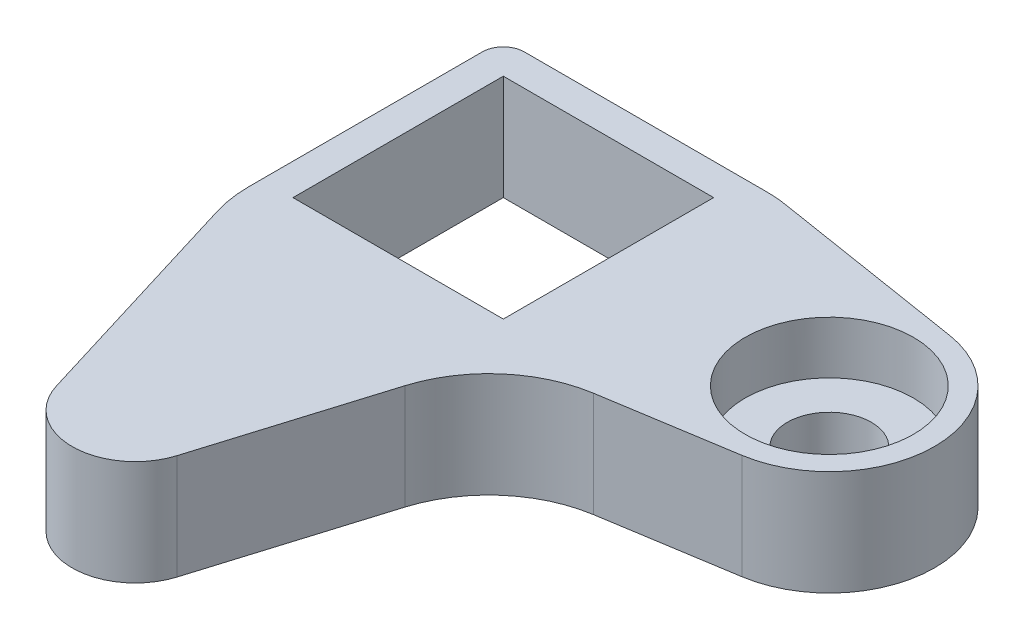
SolidWorks part; units mm, degrees
ref_plane "Front Plane" through (0, 0, 0) normal (0, 0, 1) x (1, 0, 0)
ref_plane "Top Plane" through (0, 0, 0) normal (0, 1, 0) x (1, 0, 0)
ref_plane "Right Plane" through (0, 0, 0) normal (1, 0, 0) x (0, 0, -1)
sketch "Sketch1" plane through (0, 0, 0) normal (0, 1, 0) x (1, 0, 0)
  line L0 (20, 0) -> (41, -10) construction
  line L1 (10, -45) -> (0, -20) construction
  line L2 (41, -10) -> (20, -20) construction
  line L3 (0, 0) -> (0, -20) construction
  line L4 (0, 0) -> (20, -20) construction
  line L5 (23.9399, 2.85) -> (42.5764, -0.125)
  line L12 (-3, -23) -> (23, -23) construction
  line L13 (0, 0) -> (20, 0) construction
  line L14 (0, 0) -> (0, -20) construction
  line L15 (0, -20) -> (20, -20) construction
  line L16 (20, 0) -> (20, -20) construction
  line L17 (10, -45) -> (20, -20) construction
  line L18 (-3, -21.2066) -> (-3, 1)
  line L19 (-1, 3) -> (22.0482, 3)
  line L20 (23, -23) -> (23, 3) construction
  line L21 (-3, -23) -> (23, 3) construction
  line L22 (-3, 3) -> (23, -23) construction
  line L23 (0, -20) -> (20, -20)
  line L24 (0, -20) -> (0, 0)
  line L25 (0, 0) -> (20, 0)
  line L26 (20, -20) -> (20, 0)
  line L27 (0, -20) -> (20, 0) construction
  line L28 (0, 0) -> (20, -20) construction
  line L29 (30.3947, -21.8196) -> (42.5764, -19.875)
  line L30 (20.8107, -30.1612) -> (15.7378, -46.7542)
  line L31 (-2.4757, -24.715) -> (4.2622, -46.7542)
  circle A4 centre (10, -45) radius 4 construction
  circle A5 centre (41, -10) radius 4 construction
  arc A6 (-3, 1) -> (-1, 3) centre (-1, 1) cw
  circle A7 centre (41, -10) radius 8 construction
  arc A8 (42.5764, -19.875) -> (42.5764, -0.125) centre (41, -10) ccw
  arc A9 (4.2622, -46.7542) -> (15.7378, -46.7542) centre (10, -45) ccw
  arc A10 (30.3947, -21.8196) -> (20.8107, -30.1612) centre (32.2864, -33.6695) ccw
  arc A11 (23.9399, 2.85) -> (22.0482, 3) centre (22.0482, -9) ccw
  arc A12 (-3, -21.2066) -> (-2.4757, -24.715) centre (9, -21.2066) ccw
  point P0 (10, -10)
  point P10 (10, -10)
  dimension "D6" = 8
  dimension "D7" = 16
  dimension "D8" = 20
  dimension "D9" = 12
  dimension "D10" = 12
  dimension "D11" = 12
  dimension "D5" = 2
  dimension "D2" = 20
  dimension "D3" = 3
  dimension "D4" = 45
  dimension "D12" = 20
  dimension "D13" = 41
extrude "Boss-Extrude1" add sketch "Sketch1" along normal blind 10
ref_plane "Plane1" through (0, 5, 0) normal (0, 1, 0) x (1, 0, 0)
sketch "Sketch2" plane through (0, 5, 0) normal (0, 1, 0) x (1, 0, 0)
  line L0 (20, 0) -> (41, -10) construction
  line L1 (10, -45) -> (0, -20) construction
  line L2 (41, -10) -> (20, -20) construction
  line L3 (0, 0) -> (0, -20) construction
  line L4 (0, 0) -> (20, -20) construction
  line L5 (23.9399, 2.85) -> (42.5764, -0.125) construction
  line L6 (-3, -23) -> (23, -23) construction
  line L7 (0, 0) -> (20, 0) construction
  line L8 (0, 0) -> (0, -20) construction
  line L9 (0, -20) -> (20, -20) construction
  line L10 (20, 0) -> (20, -20) construction
  line L11 (10, -45) -> (20, -20) construction
  line L12 (-3, -21.2066) -> (-3, 1) construction
  line L13 (-1, 3) -> (22.0482, 3) construction
  line L14 (23, -23) -> (23, 3) construction
  line L15 (-3, -23) -> (23, 3) construction
  line L16 (-3, 3) -> (23, -23) construction
  line L17 (0, -20) -> (20, -20) construction
  line L18 (0, -20) -> (0, 0) construction
  line L19 (0, 0) -> (20, 0) construction
  line L20 (20, -20) -> (20, 0) construction
  line L21 (0, -20) -> (20, 0) construction
  line L22 (0, 0) -> (20, -20) construction
  line L23 (30.3947, -21.8196) -> (42.5764, -19.875) construction
  line L24 (20.8107, -30.1612) -> (15.7378, -46.7542) construction
  line L25 (-2.4757, -24.715) -> (4.2622, -46.7542) construction
  circle A0 centre (10, -45) radius 4 construction
  circle A1 centre (41, -10) radius 4 construction
  arc A2 (-3, 1) -> (-1, 3) centre (-1, 1) cw construction
  circle A3 centre (41, -10) radius 8
  arc A4 (42.5764, -19.875) -> (42.5764, -0.125) centre (41, -10) ccw construction
  arc A5 (4.2622, -46.7542) -> (15.7378, -46.7542) centre (10, -45) ccw construction
  arc A6 (30.3947, -21.8196) -> (20.8107, -30.1612) centre (32.2864, -33.6695) ccw construction
  arc A7 (23.9399, 2.85) -> (22.0482, 3) centre (22.0482, -9) ccw construction
  arc A8 (-3, -21.2066) -> (-2.4757, -24.715) centre (9, -21.2066) ccw construction
  point P0 (10, -10)
  point P10 (10, -10)
  dimension "D2" = 8
  dimension "D7" = 2
  dimension "D8" = 16
  dimension "D9" = 20
  dimension "D10" = 12
  dimension "D11" = 12
  dimension "D12" = 12
  dimension "D1" = 20
  dimension "D3" = 20
  dimension "D4" = 41
  dimension "D5" = 45
  dimension "D6" = 3
sketch "Sketch3" plane through (0, 5, -5) normal (0, -1, 0) x (1, 0, 0)
  line L13 (-1, 2) -> (22.0482, 2) construction
  line L27 (-1, 2) -> (22.0482, 2) construction
  line L28 (-2.4757, 29.715) -> (4.2622, 51.7542) construction
  line L29 (20.8107, 35.1612) -> (15.7378, 51.7542) construction
  line L30 (30.3947, 26.8196) -> (42.5764, 24.875) construction
  line L31 (0, 5) -> (20, 25) construction
  line L32 (0, 25) -> (20, 5) construction
  line L33 (20, 25) -> (20, 5) construction
  line L34 (0, 5) -> (20, 5) construction
  line L35 (0, 25) -> (0, 5) construction
  line L36 (0, 25) -> (20, 25) construction
  line L37 (-3, 2) -> (23, 28) construction
  line L38 (-3, 28) -> (23, 2) construction
  line L39 (23, 28) -> (23, 2) construction
  line L40 (-3, 26.2066) -> (-3, 4) construction
  line L41 (10, 50) -> (20, 25) construction
  line L42 (20, 5) -> (20, 25) construction
  line L43 (0, 25) -> (20, 25) construction
  line L44 (0, 5) -> (0, 25) construction
  line L45 (0, 5) -> (20, 5) construction
  line L46 (-3, 28) -> (23, 28) construction
  line L47 (23.9399, 2.15) -> (42.5764, 5.125) construction
  line L48 (0, 5) -> (20, 25) construction
  line L49 (0, 5) -> (0, 25) construction
  line L50 (41, 15) -> (20, 25) construction
  line L51 (10, 50) -> (0, 25) construction
  line L52 (20, 5) -> (41, 15) construction
  arc A9 (-3, 26.2066) -> (-2.4757, 29.715) centre (9, 26.2066) cw construction
  arc A10 (23.9399, 2.15) -> (22.0482, 2) centre (22.0482, 14) cw construction
  arc A11 (30.3947, 26.8196) -> (20.8107, 35.1612) centre (32.2864, 38.6695) cw construction
  arc A12 (4.2622, 51.7542) -> (15.7378, 51.7542) centre (10, 50) cw construction
  arc A13 (42.5764, 24.875) -> (42.5764, 5.125) centre (41, 15) cw construction
  arc A14 (-3, 4) -> (-1, 2) centre (-1, 4) ccw construction
  circle A15 centre (41, 15) radius 4
  circle A16 centre (41, 15) radius 8 construction
  circle A17 centre (10, 50) radius 4
  point P112 (10, 15)
  point P113 (10, 15)
extrude "Cut-Extrude2" cut sketch "Sketch2" along normal blind 46
extrude "Cut-Extrude4" cut sketch "Sketch3" along normal blind 36
